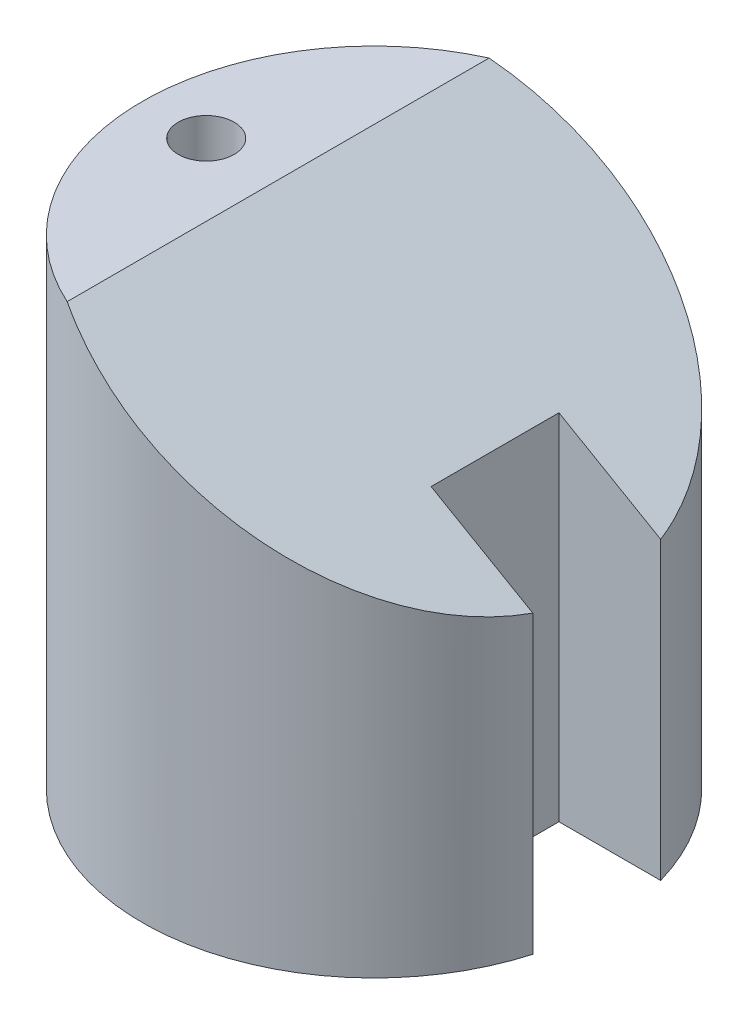
SolidWorks part; units mm, degrees
ref_plane "Front Plane" through (0, 0, 0) normal (0, 0, 1) x (1, 0, 0)
ref_plane "Top Plane" through (0, 0, 0) normal (0, 1, 0) x (1, 0, 0)
ref_plane "Right Plane" through (0, 0, 0) normal (1, 0, 0) x (0, 0, -1)
sketch "Sketch1" plane through (0, 0, 0) normal (0, 1, 0) x (1, 0, 0)
  circle A0 centre (0, 0) radius 29
  point P3 (28.7975, 3.4207)
  point P4 (34.2057, 3.7929)
  point P8 (0, 0)
  dimension "D1" = 58
extrude "Boss-Extrude1" add sketch "Sketch1" along normal blind 60
sketch "Sketch2" plane through (0, 0, 0) normal (0, 0, 1) x (1, 0, 0)
  line L0 (-12, 60) -> (29, 36.3286)
  line L1 (29, 60) -> (-29, 60) construction
  line L2 (29, 0) -> (29, 60) construction
  line L4 (-12, 60) -> (29, 60)
  line L5 (29, 60) -> (29, 36.3286)
  dimension "D1" = 30
  dimension "D2" = 17
extrude "Cut-Extrude1" cut sketch "Sketch2" against normal through all both and the other way through all
sketch "Sketch6" plane through (0, 0, 0) normal (0, 0, 1) x (1, 0, 0)
  line L0 (15.1436, 44.3286) -> (29, 36.3286)
  line L1 (29, 36.3286) -> (-12, 60) construction
  line L2 (29, 36.3286) -> (29, 0)
  line L3 (29, 0) -> (15.1436, 0)
  line L4 (-29, 0) -> (29, 0) construction
  line L5 (15.1436, 0) -> (15.1436, 44.3286)
  dimension "D1" = 16
extrude "Cut-Extrude3" cut sketch "Sketch6" against normal blind 8 and the other way blind 8
sketch "Sketch7" plane through (0, 60, 0) normal (0, 1, 0) x (1, 0, 0)
  line L0 (-12, 26.4008) -> (-12, -26.4008) construction
  circle A0 centre (-21, 0) radius 3.5
  point P2 (0, 0)
  dimension "D1" = 7
  dimension "D2" = 9
extrude "Cut-Extrude4" cut sketch "Sketch7" against normal up to next
